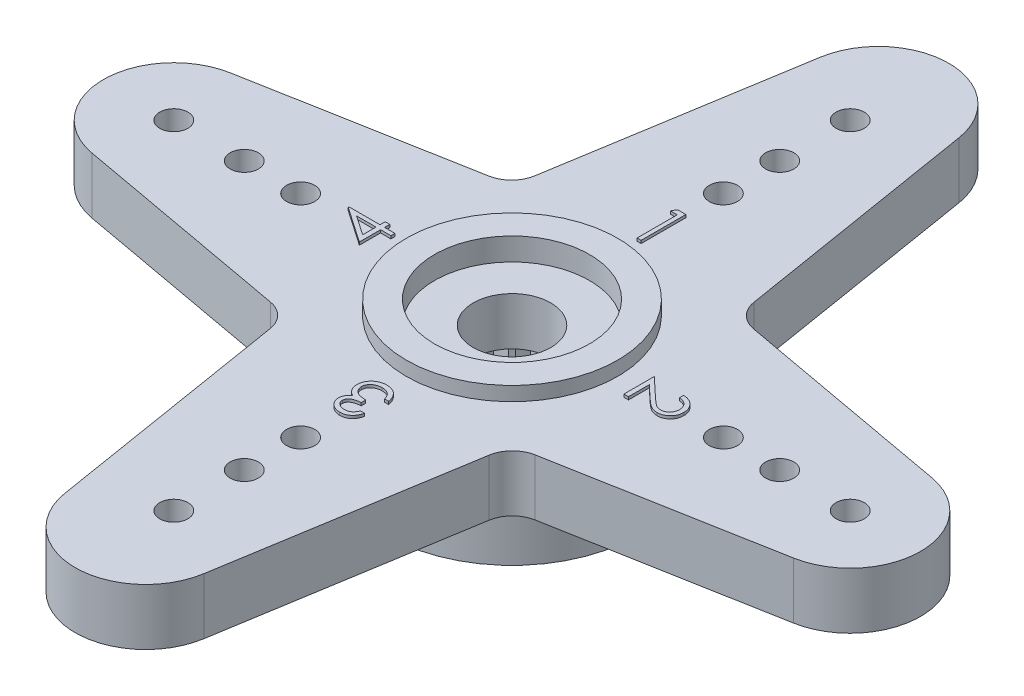
SolidWorks part; units mm, degrees
material "Nylon 101"
ref_plane "Front Plane" through (0, 0, 0) normal (0, 0, 1) x (1, 0, 0)
ref_plane "Top Plane" through (0, 0, 0) normal (0, 1, 0) x (1, 0, 0)
ref_plane "Right Plane" through (0, 0, 0) normal (1, 0, 0) x (0, 0, -1)
sketch "Sketch1" plane through (0, 0, 0) normal (0, 1, 0) x (1, 0, 0)
  line L0 (0, 15.5) -> (0, -15.5) construction
  line L1 (-15.5, 0) -> (15.5, 0) construction
  line L2 (-2.4674, 13.4022) -> (-4, 4) construction
  line L3 (4, -4) -> (-4, -4) construction
  line L4 (4, -4) -> (4, 4) construction
  line L5 (4, 4) -> (-4, 4) construction
  line L6 (-4, -4) -> (-4, 4) construction
  line L7 (4, -4) -> (-4, 4) construction
  line L8 (4, 4) -> (-4, -4) construction
  line L9 (-4, 4) -> (-2.4674, 13.4022)
  line L10 (4, 4) -> (2.4674, 13.4022)
  line L11 (4, -4) -> (2.4674, -13.4022)
  line L12 (-4, -4) -> (-2.4674, -13.4022)
  line L13 (-4, 4) -> (-12.5927, 2.4331) construction
  line L14 (-4, 4) -> (-12.4485, 2.4594)
  line L15 (-4, -4) -> (-12.4485, -2.4594)
  line L16 (4, -4) -> (12.4485, -2.4594)
  line L17 (4, 4) -> (12.4485, 2.4594)
  circle A0 centre (0, 0) radius 15.5 construction
  circle A1 centre (0, 0) radius 14.5 construction
  arc A2 (2.4674, 13.4022) -> (-2.4674, 13.4022) centre (0, 13) ccw
  arc A3 (2.4674, -13.4022) -> (-2.4674, -13.4022) centre (0, -13) cw
  arc A4 (-12.4485, 2.4594) -> (-12.4485, -2.4594) centre (-12, 0) ccw
  arc A5 (12.4485, 2.4594) -> (12.4485, -2.4594) centre (12, 0) cw
  circle A6 centre (0, 0) radius 12 construction
  circle A7 centre (0, 0) radius 9.5 construction
  circle A8 centre (0, 0) radius 7.5 construction
  circle A9 centre (0, 12) radius 0.5
  circle A10 centre (0, 9.5) radius 0.5
  circle A11 centre (0, 7.5) radius 0.5
  circle A12 centre (12, 0) radius 0.5
  circle A13 centre (9.5, 0) radius 0.5
  circle A14 centre (7.5, 0) radius 0.5
  circle A15 centre (0, -12) radius 0.5
  circle A16 centre (0, -9.5) radius 0.5
  circle A17 centre (0, -7.5) radius 0.5
  circle A18 centre (-12, 0) radius 0.5
  circle A19 centre (-9.5, 0) radius 0.5
  circle A20 centre (-7.5, 0) radius 0.5
  circle A21 centre (0, 0) radius 1.375
  point P59 (0, 0)
  dimension "D1" = 31
  dimension "D2" = 1
  dimension "D3" = 5
  dimension "D4" = 5
  dimension "D5" = 8
  dimension "D6" = 8
  dimension "D7" = 15
  dimension "D9" = 24
  dimension "D11" = 1
  dimension "D12" = 1
  dimension "D13" = 4
  dimension "D8" = 19
  dimension "D10" = 1
  dimension "D14" = 2.75
extrude "Boss-Extrude1" add sketch "Sketch1" along normal blind 2
sketch "Sketch2" plane through (0, 2, 0) normal (0, 1, 0) x (1, 0, 0)
  circle A0 centre (0, 0) radius 3.75
  circle A1 centre (0, 0) radius 2.75
  dimension "D1" = 7.5
  dimension "D2" = 1
extrude "Boss-Extrude2" add sketch "Sketch2" along normal blind 0.5
sketch "Sketch3" plane through (0, 2.5, 0) normal (0, 1, 0) x (1, 0, 0)
  circle A2 centre (0, 0) radius 1.375
  circle A3 centre (0, 0) radius 2.75
  circle A5 centre (0, 0) radius 2.75
  circle A6 centre (0, 0) radius 2.75
  circle M6 centre (0, 0) radius 2.75
  dimension "D1" = 0
extrude "Cut-Extrude1" cut sketch "Sketch3" against normal blind 0.8 contours A2 M6 region at (-2.6722, 2.5, 0)
sketch "Sketch4" plane through (0, 0, 0) normal (0, -1, 0) x (1, 0, 0)
  circle A0 centre (0, 0) radius 4.5
  circle A1 centre (0, 0) radius 2.5
  dimension "D1" = 9
  dimension "D2" = 2
extrude "Boss-Extrude3" add sketch "Sketch4" along normal blind 2.5
sketch "Sketch5" plane through (0, -2.5, 0) normal (0, -1, 0) x (1, 0, 0)
  line L0 (0, 0) -> (0, 0.6245) construction
  line L1 (0, 3) -> (-0.299, 2.4821)
  line L2 (0, 3) -> (0.299, 2.4821)
  line L3 (0.9271, 2.8532) -> (0.4826, 2.453)
  line L4 (0.9271, 2.8532) -> (1.0514, 2.2682)
  line L5 (1.7634, 2.4271) -> (1.217, 2.1838)
  line L6 (1.7634, 2.4271) -> (1.7008, 1.8323)
  line L7 (2.4271, 1.7634) -> (1.8323, 1.7008)
  line L8 (2.4271, 1.7634) -> (2.1838, 1.217)
  line L9 (2.8532, 0.9271) -> (2.2682, 1.0514)
  line L10 (2.8532, 0.9271) -> (2.453, 0.4826)
  line L11 (3, 0) -> (2.4821, 0.299)
  line L12 (3, 0) -> (2.4821, -0.299)
  line L13 (2.8532, -0.9271) -> (2.453, -0.4826)
  line L14 (2.8532, -0.9271) -> (2.2682, -1.0514)
  line L15 (2.4271, -1.7634) -> (2.1838, -1.217)
  line L16 (2.4271, -1.7634) -> (1.8323, -1.7008)
  line L17 (1.7634, -2.4271) -> (1.7008, -1.8323)
  line L18 (1.7634, -2.4271) -> (1.217, -2.1838)
  line L19 (0.9271, -2.8532) -> (1.0514, -2.2682)
  line L20 (0.9271, -2.8532) -> (0.4826, -2.453)
  line L21 (0, -3) -> (0.299, -2.4821)
  line L22 (0, -3) -> (-0.299, -2.4821)
  line L23 (-0.9271, -2.8532) -> (-0.4826, -2.453)
  line L24 (-0.9271, -2.8532) -> (-1.0514, -2.2682)
  line L25 (-1.7634, -2.4271) -> (-1.217, -2.1838)
  line L26 (-1.7634, -2.4271) -> (-1.7008, -1.8323)
  line L27 (-2.4271, -1.7634) -> (-1.8323, -1.7008)
  line L28 (-2.4271, -1.7634) -> (-2.1838, -1.217)
  line L29 (-2.8532, -0.9271) -> (-2.2682, -1.0514)
  line L30 (-2.8532, -0.9271) -> (-2.453, -0.4826)
  line L31 (-3, 0) -> (-2.4821, -0.299)
  line L32 (-3, 0) -> (-2.4821, 0.299)
  line L33 (-2.8532, 0.9271) -> (-2.453, 0.4826)
  line L34 (-2.8532, 0.9271) -> (-2.2682, 1.0514)
  line L35 (-2.4271, 1.7634) -> (-2.1838, 1.217)
  line L36 (-2.4271, 1.7634) -> (-1.8323, 1.7008)
  line L37 (-1.7634, 2.4271) -> (-1.7008, 1.8323)
  line L38 (-1.7634, 2.4271) -> (-1.217, 2.1838)
  line L39 (-0.9271, 2.8532) -> (-1.0514, 2.2682)
  line L40 (-0.9271, 2.8532) -> (-0.4826, 2.453)
  circle A0 centre (0, 0) radius 2.5 construction
  arc A1 (-2.1838, 1.217) -> (-2.2682, 1.0514) centre (0, 0) ccw
  arc A2 (-1.7008, 1.8323) -> (-1.8323, 1.7008) centre (0, 0) ccw
  arc A3 (-1.0514, 2.2682) -> (-1.217, 2.1838) centre (0, 0) ccw
  arc A4 (-0.299, 2.4821) -> (-0.4826, 2.453) centre (0, 0) ccw
  arc A5 (0.4826, 2.453) -> (0.299, 2.4821) centre (0, 0) ccw
  arc A6 (1.217, 2.1838) -> (1.0514, 2.2682) centre (0, 0) ccw
  arc A7 (1.8323, 1.7008) -> (1.7008, 1.8323) centre (0, 0) ccw
  arc A8 (2.2682, 1.0514) -> (2.1838, 1.217) centre (0, 0) ccw
  arc A9 (2.4821, 0.299) -> (2.453, 0.4826) centre (0, 0) ccw
  arc A10 (2.453, -0.4826) -> (2.4821, -0.299) centre (0, 0) ccw
  arc A11 (2.1838, -1.217) -> (2.2682, -1.0514) centre (0, 0) ccw
  arc A12 (1.7008, -1.8323) -> (1.8323, -1.7008) centre (0, 0) ccw
  arc A13 (1.0514, -2.2682) -> (1.217, -2.1838) centre (0, 0) ccw
  arc A14 (0.299, -2.4821) -> (0.4826, -2.453) centre (0, 0) ccw
  arc A15 (-0.4826, -2.453) -> (0, -2.5) centre (0, 0) ccw
  arc A16 (-1.217, -2.1838) -> (-1.0514, -2.2682) centre (0, 0) ccw
  arc A17 (-1.8323, -1.7008) -> (-1.7008, -1.8323) centre (0, 0) ccw
  arc A18 (-2.2682, -1.0514) -> (-2.1838, -1.217) centre (0, 0) ccw
  arc A19 (-2.4821, -0.299) -> (-2.453, -0.4826) centre (0, 0) ccw
  arc A20 (-2.453, 0.4826) -> (-2.4821, 0.299) centre (0, 0) ccw
  point P68 (0, 0)
  circle M5 centre (0, 0) radius 2.5
  dimension "D1" = 30
  dimension "D2" = 3
  dimension "D3" = 20
extrude "Cut-Extrude3" cut sketch "Sketch5" against normal up to surface (2.5 mm away) contours L36 L35 M5 | L34 L33 M5 | L32 L31 M5 | L30 L29 M5 | L28 L27 M5 | L26 L25 M5 | L24 L23 M5 | L0 L21 M5 | L22 L0 M5 | L20 L19 M5 | L18 L17 M5 | L16 L15 M5 | L14 L13 M5 | L12 L11 M5 | L10 L9 M5 | L8 L7 M5 | L6 L5 M5 | L4 L3 M5 | L0 L2 M5 | L0 L1 M5 | L40 L39 M5 | L38 L37 M5 region at (0, -2.5, 2.6627) region at (-0.8228, -2.5, 2.5324) region at (0.8228, -2.5, 2.5324) region at (-1.5651, -2.5, 2.1542) region at (1.5651, -2.5, 2.1542) region at (-2.1542, -2.5, 1.5651) region at (2.1542, -2.5, 1.5651) region at (-2.5324, -2.5, 0.8228) region at (2.5324, -2.5, 0.8228) region at (-2.6627, -2.5, 0) region at (2.6627, -2.5, 0) region at (-2.5324, -2.5, -0.8228) region at (2.5324, -2.5, -0.8228) region at (-2.1542, -2.5, -1.5651) region at (2.1542, -2.5, -1.5651) region at (-1.5651, -2.5, -2.1542) region at (1.5651, -2.5, -2.1542) region at (-0.8228, -2.5, -2.5324) region at (0.8228, -2.5, -2.5324) region at (0, -2.5, -2.6627) up to face at (0, 0, 1.375)
sketch "Sketch6" plane through (0, 2, 0) normal (0, 1, 0) x (1, 0, 0)
  line L1 (4.5, -4.5) -> (-4.5, -4.5) construction
  line L2 (4.5, -4.5) -> (4.5, 4.5) construction
  line L3 (4.5, 4.5) -> (-4.5, 4.5) construction
  line L4 (-4.5, -4.5) -> (-4.5, 4.5) construction
  line L5 (4.5, -4.5) -> (-4.5, 4.5) construction
  line L6 (4.5, 4.5) -> (-4.5, -4.5) construction
  circle A0 centre (0, 0) radius 4.5 construction
  text T0 "1" font "Century Gothic" height in points 6
  text T1 "2" font "Century Gothic" height in points 6
  text T2 "3" font "Century Gothic" height in points 6
  text T3 "4" font "Century Gothic" height in points 6
  dimension "D1" = 9
  dimension "D2" = 9
  dimension "D3" = 9
extrude "Boss-Extrude4" add sketch "Sketch6" along normal blind 0.1
fillet "Fillet1" radius 1 4 edges at (-4, 1, -4) (-4, 1, 4) (4, 1, 4) (4, 1, -4)
